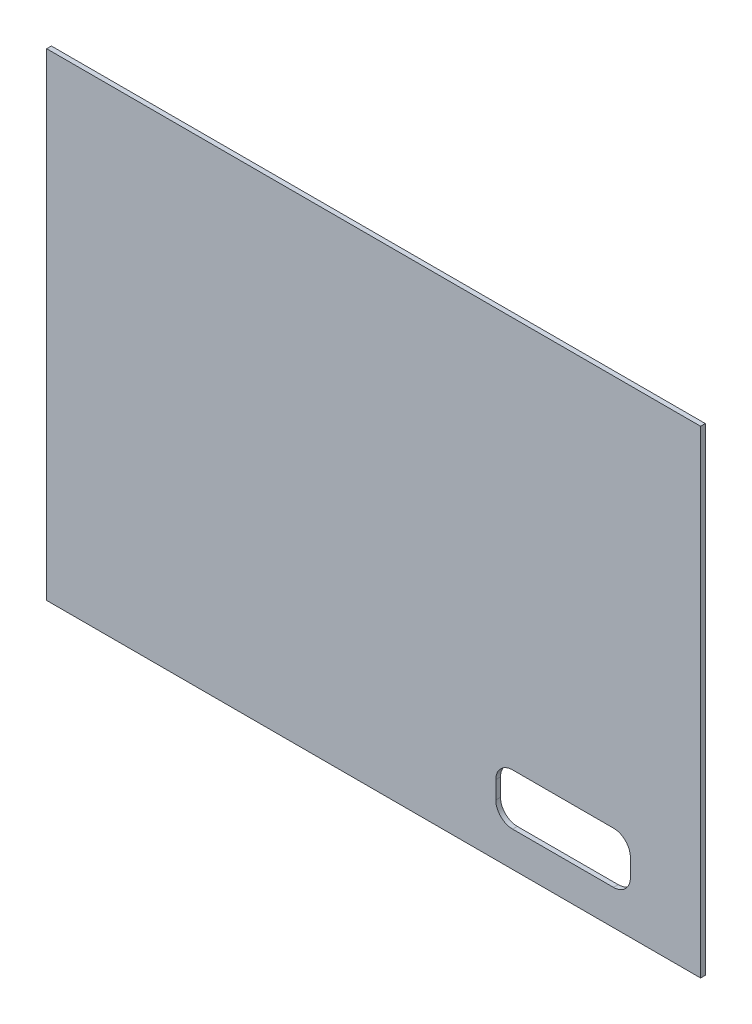
SolidWorks part; units mm, degrees
ref_plane "Front Plane" through (0, 0, 0) normal (0, 0, 1) x (1, 0, 0)
ref_plane "Top Plane" through (0, 0, 0) normal (0, 1, 0) x (1, 0, 0)
ref_plane "Right Plane" through (0, 0, 0) normal (1, 0, 0) x (0, 0, -1)
sketch "Sketch1" plane through (0, 0, 0) normal (0, 0, 1) x (1, 0, 0)
  line L0 (25.5163, 88.5062) -> (25.5163, -23.5303) construction
  line L1 (0, 0) -> (97.1664, 0)
  line L2 (0, 0) -> (0, 71)
  line L3 (0, 71) -> (97.1664, 71)
  line L4 (97.1664, 0) -> (97.1664, 71)
  line L5 (15.5163, 88.5062) -> (15.5163, -23.5303) construction
  line L6 (10.5163, 65) -> (20.5163, 65)
  line L7 (10.5163, 65) -> (15.5163, 53)
  line L8 (15.5163, 53) -> (20.5163, 65)
  line L9 (25.5163, 65) -> (25.5163, 54)
  line L10 (25.5163, 54) -> (18.2663, 36.6)
  line L11 (18.2663, 36.6) -> (18.2663, 47.6)
  line L12 (18.2663, 47.6) -> (25.5163, 65)
  line L13 (5.5163, 65) -> (12.7663, 47.6)
  line L14 (12.7663, 47.6) -> (12.7663, 36.6)
  line L15 (12.7663, 36.6) -> (5.5163, 54)
  line L16 (5.5163, 54) -> (5.5163, 65)
  line L17 (72.655, 88.5062) -> (72.655, -23.5303) construction
  line L18 (84.4001, 47.6) -> (91.6501, 65)
  line L19 (81.6501, 53) -> (86.6501, 65)
  line L20 (76.6501, 65) -> (86.6501, 65)
  line L21 (91.6501, 54) -> (84.4001, 36.6)
  line L22 (79.905, 36.6) -> (72.655, 54)
  line L23 (76.6501, 65) -> (81.6501, 53)
  line L24 (72.655, 65) -> (79.905, 47.6)
  line L25 (91.6501, 65) -> (91.6501, 54)
  line L26 (84.4001, 36.6) -> (84.4001, 47.6)
  line L27 (79.905, 47.6) -> (79.905, 36.6)
  line L28 (72.655, 54) -> (72.655, 65)
  line L29 (66.7319, 90.2077) -> (66.7319, -23.5303) construction
  line L30 (18.5163, 47.55) -> (25.2663, 63.75)
  line L31 (66.7319, 5.1907) -> (86.7319, 5.1907)
  line L32 (66.7319, 5.1907) -> (66.7319, 12.8107)
  line L33 (66.7319, 12.8107) -> (86.7319, 12.8107)
  line L34 (86.7319, 5.1907) -> (86.7319, 12.8107)
  line L35 (25.2663, 63.75) -> (25.2663, 54.05)
  line L36 (25.2663, 54.05) -> (18.5163, 37.85)
  line L37 (18.5163, 37.85) -> (18.5163, 47.55)
  line L38 (15.5163, 53.65) -> (20.1413, 64.75)
  line L39 (10.8913, 64.75) -> (20.1413, 64.75)
  line L40 (10.8913, 64.75) -> (15.5163, 53.65)
  line L41 (5.7663, 54.05) -> (5.7663, 63.75)
  line L42 (5.7663, 63.75) -> (12.5163, 47.55)
  line L43 (12.5163, 47.55) -> (12.5163, 37.85)
  line L44 (12.5163, 37.85) -> (5.7663, 54.05)
  line L45 (79.655, 37.85) -> (72.905, 54.05)
  line L46 (72.905, 54.05) -> (72.905, 63.75)
  line L47 (72.905, 63.75) -> (79.655, 47.55)
  line L48 (79.655, 47.55) -> (79.655, 37.85)
  line L49 (81.6501, 53.65) -> (86.2751, 64.75)
  line L50 (77.0251, 64.75) -> (86.2751, 64.75)
  line L51 (77.0251, 64.75) -> (81.6501, 53.65)
  line L52 (84.6501, 47.55) -> (91.4001, 63.75)
  line L53 (91.4001, 63.75) -> (91.4001, 54.05)
  line L54 (91.4001, 54.05) -> (84.6501, 37.85)
  line L55 (84.6501, 37.85) -> (84.6501, 47.55)
  point P12 (15.5163, 65)
  point P26 (81.644, 65)
  dimension "D1" = 97.1664
  dimension "D2" = 71
  dimension "D3" = 25.5163
  dimension "D4" = 10
  dimension "D5" = 10
  dimension "D6" = 12
  dimension "D7" = 11
  dimension "D8" = 28.4
  dimension "D9" = 28.4
  dimension "D10" = 5
  dimension "D11" = 2.75
  dimension "D12" = 6
  dimension "D13" = 24.5115
  dimension "D14" = 0
  dimension "D15" = 30.4345
  dimension "D16" = 5.1907
  dimension "D17" = 7.62
  dimension "D18" = 20
  dimension "D19" = 0.25
extrude "Boss-Extrude2" add sketch "Sketch1" along normal blind 0.7 contours L2 L1 L4 L3 | L32 L31 L34 L33
extrude "Boss-Extrude3" add sketch "Sketch1<4>" against normal blind 5 contours L37 L36 L35 L30 | L39 L40 L38 | L44 L43 L42 L41 | L50 L51 L49 | L48 L47 L46 L45 | L55 L54 L53 L52 region at (21.8913, 50.8, 0) region at (15.5163, 61.05, 0) region at (9.1413, 50.8, 0) region at (76.28, 50.8, 0) region at (81.6501, 61.05, 0) region at (88.0251, 50.8, 0)
sketch "Sketch1<4>" plane through (0, 0, 0) normal (0, 0, 1) x (1, 0, 0) same geometry as "Sketch1"
fillet "Fillet1" radius 2.5 4 edges at (66.7319, 5.1907, 0.35) (66.7319, 12.8107, 0.35) (86.7319, 12.8107, 0.35) (86.7319, 5.1907, 0.35)
